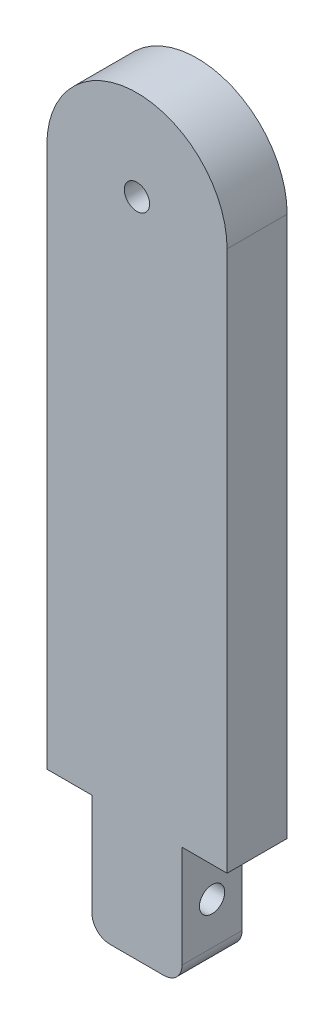
SolidWorks part; units mm, degrees
ref_plane "前视基准面" through (0, 0, 0) normal (0, 0, 1) x (1, 0, 0)
ref_plane "上视基准面" through (0, 0, 0) normal (0, 1, 0) x (1, 0, 0)
ref_plane "右视基准面" through (0, 0, 0) normal (1, 0, 0) x (0, 0, -1)
other "Configuration Table"
sketch "草图1" plane through (0, 0, 0) normal (0, 0, 1) x (1, 0, 0)
  line L1 (0, 0) -> (30, 0)
  line L2 (0, 0) -> (0, 125)
  line L3 (0, 125) -> (30, 125)
  line L4 (30, 0) -> (30, 125)
  dimension "D1" = 30
  dimension "D2" = 125
extrude "凸台-拉伸1" add sketch "草图1" along normal blind 10
sketch "草图2" plane through (0, 0, 10) normal (0, 0, 1) x (1, 0, 0)
  line L0 (0, 20) -> (7.5, 20)
  line L1 (0, 125) -> (0, 0) construction
  line L2 (7.5, 20) -> (7.5, 0)
  line L3 (0, 0) -> (30, 0) construction
  line L4 (30, 20) -> (22.5, 20)
  line L5 (30, 0) -> (30, 125) construction
  line L6 (22.5, 20) -> (22.5, 0)
  line L7 (15, 0) -> (15, 125) construction
  line L8 (30, 125) -> (0, 125) construction
  line L9 (30, 20) -> (30, 0)
  line L10 (30, 0) -> (22.5, 0)
  line L11 (0, 20) -> (0, 0)
  line L12 (0, 0) -> (7.5, 0)
  dimension "D1" = 15
  dimension "D2" = 20
extrude "切除-拉伸1" cut sketch "草图2" against normal blind 10
fillet "圆角1" radius 3 2 edges at (22.5, 0, 5) (7.5, 0, 5)
sketch "草图3" plane through (0, 0, 0) normal (-1, 0, 0) x (0, 0, 1)
  line L0 (5, 125) -> (5, 0) construction
  line L1 (10, 125) -> (0, 125) construction
  line L2 (10, 0) -> (0, 0) construction
  circle A0 centre (5, 10) radius 2.1
  dimension "D1" = 4.2
  dimension "D2" = 10
extrude "切除-拉伸2" cut sketch "草图3" against normal through all
fillet "圆角2" 2 edges at (30, 125, 5) (0, 125, 5) type full round first side face at (30, 72.5, 5) second side face at (0, 72.5, 5) middle face at (15, 125, 5)
sketch "草图4" plane through (0, 0, 0) normal (0, 0, -1) x (-1, 0, 0)
  circle A0 centre (-15, 110) radius 2.1
  dimension "D1" = 4.2
extrude "切除-拉伸3" cut sketch "草图4" against normal through all
